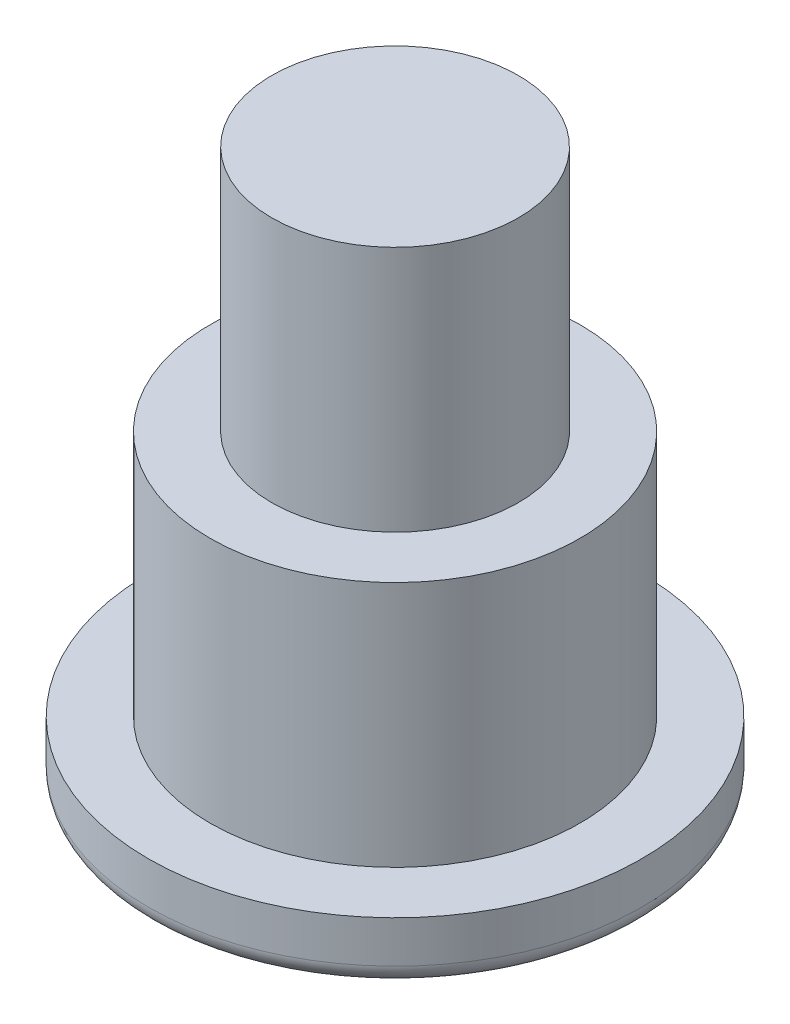
SolidWorks part; units mm, degrees
material "PET"
ref_plane "Front Plane" through (0, 0, 0) normal (0, 0, 1) x (1, 0, 0)
ref_plane "Top Plane" through (0, 0, 0) normal (0, 1, 0) x (1, 0, 0)
ref_plane "Right Plane" through (0, 0, 0) normal (1, 0, 0) x (0, 0, -1)
ref_axis "X-Axis" through (-88.99, 0, 0) along (1, 0, 0)
ref_axis "Y-Axis" through (0, 55, 0) along (0, -1, 0)
ref_axis "Z-Axis" through (0, 0, -88.99) along (0, 0, 1)
sketch "Sketch1" plane through (0, 0, 0) normal (0, 1, 0) x (1, 0, 0)
  circle A0 centre (0, 0) radius 3.175
  dimension "D1" = 6.35
extrude "Boss-Extrude1" add sketch "Sketch1" along normal blind 0.7937
ref_plane "Plane1" through (0, 0.7937, 0) normal (0, 1, 0) x (1, 0, 0)
sketch "Sketch2" plane through (0, 0.7937, 0) normal (0, 1, 0) x (1, 0, 0)
  circle A0 centre (0, 0) radius 2.3813
  dimension "D1" = 4.7625
extrude "Boss-Extrude2" add sketch "Sketch2" along normal blind 3.175
ref_plane "Plane2" through (0, 3.9688, 0) normal (0, 1, 0) x (1, 0, 0)
sketch "Sketch3" plane through (0, 3.9688, 0) normal (0, 1, 0) x (1, 0, 0)
  circle A0 centre (0, 0) radius 1.5875
  dimension "D1" = 3.175
extrude "Boss-Extrude3" add sketch "Sketch3" along normal blind 3.175
fillet "Fillet1" radius 0.254 1 edges at (0, 0, 3.175)
